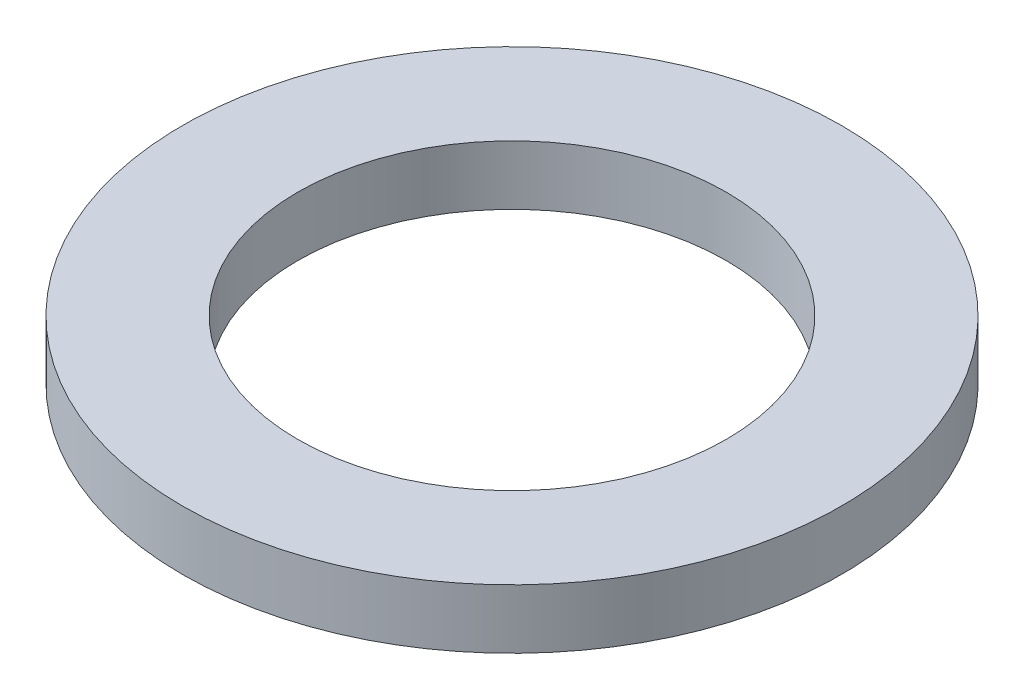
SolidWorks part; units mm, degrees
ref_plane "Front Plane" through (0, 0, 0) normal (0, 0, 1) x (1, 0, 0)
ref_plane "Top Plane" through (0, 0, 0) normal (0, 1, 0) x (1, 0, 0)
ref_plane "Right Plane" through (0, 0, 0) normal (1, 0, 0) x (0, 0, -1)
sketch "Sketch1" plane through (0, 0, 0) normal (0, 1, 0) x (1, 0, 0)
  circle A0 centre (0, 0) radius 50
  dimension "FLANGE_OD" = 100
extrude "Boss-Extrude1" add sketch "Sketch1" along normal blind 9
sketch "Sketch2" plane through (0, 0, 0) normal (0, 1, 0) x (1, 0, 0)
  circle A0 centre (0, 0) radius 32.5
  dimension "BORE_D" = 65
extrude "Cut-Extrude1" cut sketch "Sketch2" along normal through all
sketch "Sketch3" plane through (0, 9, 0) normal (0, 1, 0) x (1, 0, 0)
  circle A0 centre (0, 0) radius 18.7507 construction
  circle A1 centre (-18.7507, 0) radius 1.8747
  dimension "BOLT_D" = 3.7493
  dimension "BOLT_PCD" = 37.5014
extrude "Cut-Extrude2" cut sketch "Sketch3" against normal blind 7.577 rebuild error yes
pattern_circular "CirPattern1" count 4 over 360 rebuild error yes
